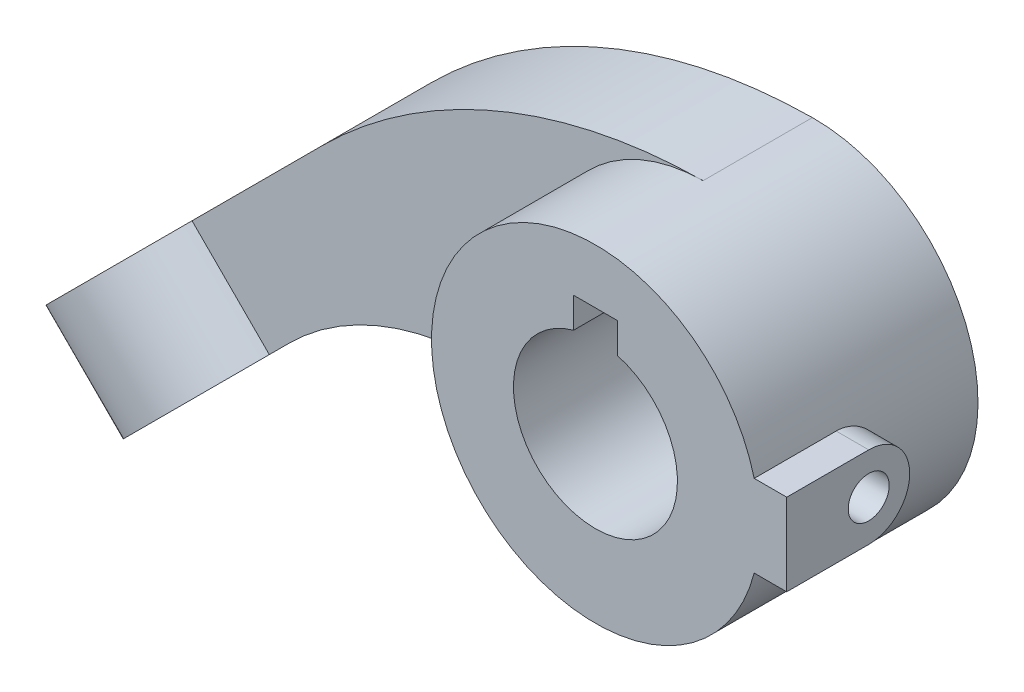
SolidWorks part; units mm, degrees
ref_plane "前视基准面" through (0, 0, 0) normal (0, 0, 1) x (1, 0, 0)
ref_plane "上视基准面" through (0, 0, 0) normal (0, 1, 0) x (1, 0, 0)
ref_plane "右视基准面" through (0, 0, 0) normal (1, 0, 0) x (0, 0, -1)
other "Configuration Table"
sketch "草图1" plane through (0, 0, 0) normal (0, 0, 1) x (1, 0, 0)
  line L0 (0, 30.9602) -> (0, -122.1414) construction
  line L4 (0, 0) -> (103.3717, 0) construction
  line L5 (-4, 20) -> (4, 20)
  line L6 (-4, 20) -> (-4, 14.4568)
  line L7 (4, 20) -> (4, 14.4568)
  line L8 (-106.066, -35.3553) -> (-91.9239, -49.4975)
  line L9 (-91.9239, -49.4975) -> (-75.9855, -33.5591)
  line L10 (-106.066, -35.3553) -> (-69.9964, 0.7143)
  arc A0 (-4, 14.4568) -> (4, 14.4568) centre (0, 0) ccw
  circle A1 centre (0, 0) radius 30
  arc A2 (-69.9964, 0.7143) -> (-0.3061, 29.9984) centre (0.7143, -69.9964) cw
  arc A3 (-75.9855, -33.5591) -> (-15.2363, -25.8429) centre (-40.6301, -68.9144) cw
  point P22 (-23.8265, 18.229)
  point P23 (-25.0567, -16.4973)
  dimension "D1" = 30
  dimension "D2" = 60
  dimension "D11" = 100
  dimension "D12" = 50
  dimension "D5" = 20
  dimension "D6" = 8
  dimension "D7" = 100
  dimension "D8" = 20
  dimension "D9" = 50
  dimension "D10" = 45
extrude "凸台-拉伸1" add sketch "草图1" along normal blind 40 contours A1 A0 L6 L5 L7 region at (20.5078, 20.7181, 0)
extrude "凸台-拉伸2" add sketch "草图1<3>" along normal blind 20 contours L9 A3 A1 A2 L10 L8 region at (-58.5321, -9.5795, 0)
sketch "草图1<3>" plane through (0, 0, 0) normal (0, 0, 1) x (1, 0, 0) same geometry as "草图1"
sketch "草图2" plane through (-21.2132, 21.2132, 0) normal (0.7071, -0.7071, 0) x (0, 0, -1)
  line L0 (-20, -100) -> (0, -100) construction
  circle A0 centre (-10, -100) radius 20
  circle A1 centre (-10, -100) radius 10
  line M4 (-20, -100) -> (0, -100)
  dimension "D1" = 20
  dimension "D2" = 40
extrude "凸台-拉伸3" add sketch "草图2" against normal blind 20
extrude "切除-拉伸1" cut sketch "草图2<3>" against normal blind 20 contours A1 M4 region at (-88.9228, -46.4964, 10)
sketch "草图2<3>" plane through (-21.2132, 21.2132, 0) normal (0.7071, -0.7071, 0) x (0, 0, -1) same geometry as "草图2"
ref_plane "基准面1" through (35, 0, 0) normal (1, 0, 0) x (0, 0, -1)
sketch "草图3" plane through (35, 0, 0) normal (1, 0, 0) x (0, 0, -1)
  line L0 (0, 0) -> (-54.6634, 0) construction
  line L1 (-25, 7.5) -> (-40, 7.5)
  line L2 (-40, 30) -> (-40, -30) construction
  line L3 (-25, -7.5) -> (-40, -7.5)
  line L4 (-40, 7.5) -> (-40, -7.5)
  arc A0 (-25, -7.5) -> (-25, 7.5) centre (-25, 0) ccw
  circle A1 centre (-25, 0) radius 3.75
  dimension "D1" = 7.5
  dimension "D2" = 15
  dimension "D3" = 15
extrude "凸台-拉伸4" add sketch "草图3" against normal up to next
extrude "切除-拉伸2" cut sketch "草图3<2>" against normal up to next contours A1
sketch "草图3<2>" plane through (35, 0, 0) normal (1, 0, 0) x (0, 0, -1) same geometry as "草图3"
